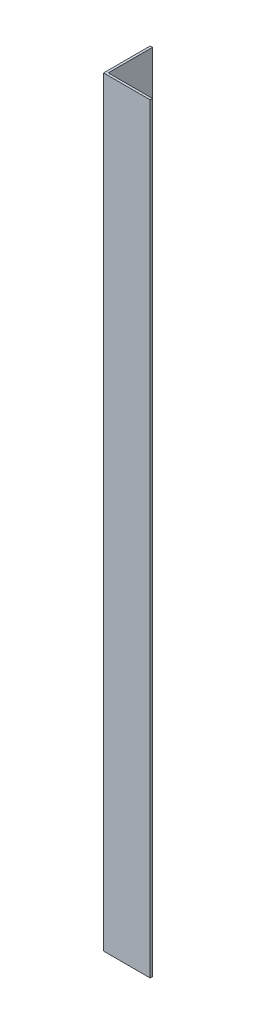
SolidWorks part; units mm, degrees
material "1060 Сплав"
ref_plane "Спереди" through (0, 0, 0) normal (0, 0, 1) x (1, 0, 0)
ref_plane "Сверху" through (0, 0, 0) normal (0, 1, 0) x (1, 0, 0)
ref_plane "Справа" through (0, 0, 0) normal (1, 0, 0) x (0, 0, -1)
sketch "Эскиз1" plane through (0, 0, 0) normal (0, 1, 0) x (1, 0, 0)
  line L0 (0, 0) -> (0, 15)
  line L1 (0, 15) -> (0.75, 15)
  line L2 (0.75, 15) -> (0.75, 0.75)
  line L3 (0.75, 0.75) -> (15, 0.75)
  line L4 (15, 0.75) -> (15, 0)
  line L5 (15, 0) -> (0, 0)
  dimension "D1" = 0.75
  dimension "D2" = 15
extrude "Бобышка-Вытянуть1" add sketch "Эскиз1" along normal blind 245
